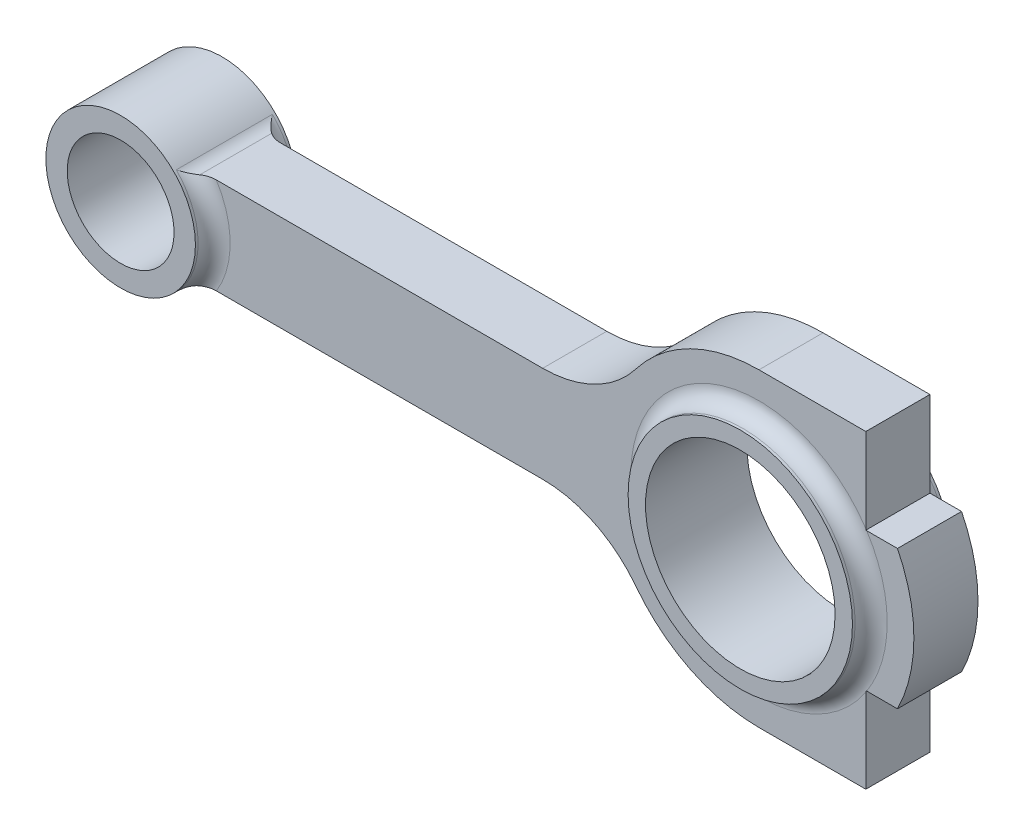
SolidWorks part; units mm, degrees
ref_plane "Front Plane" through (0, 0, 0) normal (0, 0, 1) x (1, 0, 0)
ref_plane "Top Plane" through (0, 0, 0) normal (0, 1, 0) x (1, 0, 0)
ref_plane "Right Plane" through (0, 0, 0) normal (1, 0, 0) x (0, 0, -1)
sketch "Sketch1" plane through (0, 0, 0) normal (0, 0, 1) x (1, 0, 0)
  line L0 (0, 0) -> (116, 0) construction
  line L1 (116, 29) -> (136, 29)
  line L2 (116, -29) -> (136, -29)
  line L4 (12.0416, 9) -> (75.5031, 9)
  line L5 (12.0416, -9) -> (75.5031, -9)
  line L7 (136, 29) -> (136, 13)
  line L8 (136, -29) -> (136, -13)
  line L9 (136, 13) -> (141.923, 13)
  line L10 (136, -13) -> (141.923, -13)
  circle A0 centre (0, 0) radius 10
  arc A1 (9.9166, 9.8824) -> (9.9166, -9.8824) centre (0, 0) ccw
  arc A2 (116, 29) -> (92.9723, 17.6275) centre (116, 0) ccw
  circle A3 centre (116, 0) radius 21
  circle A4 centre (116, 0) radius 17.75
  arc A5 (141.923, -13) -> (141.923, 13) centre (116, 0) ccw
  arc A6 (92.9723, -17.6275) -> (116, -29) centre (116, 0) ccw
  arc A7 (92.9723, 17.6275) -> (75.5031, 9) centre (75.5031, 31) cw
  arc A8 (92.9723, -17.6275) -> (75.5031, -9) centre (75.5031, -31) ccw
  arc A9 (9.9166, 9.8824) -> (12.0416, 9) centre (12.0416, 12) ccw
  arc A10 (9.9166, -9.8824) -> (12.0416, -9) centre (12.0416, -12) cw
  circle A11 centre (0, 0) radius 14
  dimension "D1" = 28
  dimension "D2" = 20
  dimension "D4" = 35.5
  dimension "D9" = 22
  dimension "D10" = 22
  dimension "D11" = 3
  dimension "D12" = 3
  dimension "D3" = 116
  dimension "D5" = 20
  dimension "D6" = 20
  dimension "D7" = 16
  dimension "D8" = 16
extrude "Boss-Extrude3" add sketch "Sketch1" along normal blind 12 contours A11 A10 L5 A8 A6 L2 L8 L10 A5 L9 L7 L1 A2 A7 L4 A9 A3 region at (82.8182, 0, 0)
extrude "Boss-Extrude6" add sketch "Sketch1<12>" along normal blind 15.5 contours A3
sketch "Sketch1<12>" plane through (0, 0, 0) normal (0, 0, 1) x (1, 0, 0) same geometry as "Sketch1"
extrude "Boss-Extrude7" add sketch "Sketch1<13>" against normal blind 3.5 contours A3
sketch "Sketch1<13>" plane through (0, 0, 0) normal (0, 0, 1) x (1, 0, 0) same geometry as "Sketch1"
extrude "Cut-Extrude2" cut sketch "Sketch1<15>" along normal mid plane 100 contours A4
sketch "Sketch1<15>" plane through (0, 0, 0) normal (0, 0, 1) x (1, 0, 0) same geometry as "Sketch1"
extrude "Boss-Extrude9" add sketch "Sketch1<17>" along normal blind 15.5 contours A11
sketch "Sketch1<17>" plane through (0, 0, 0) normal (0, 0, 1) x (1, 0, 0) same geometry as "Sketch1"
extrude "Boss-Extrude10" add sketch "Sketch1<18>" against normal blind 3.5 contours A11
sketch "Sketch1<18>" plane through (0, 0, 0) normal (0, 0, 1) x (1, 0, 0) same geometry as "Sketch1"
extrude "Cut-Extrude3" cut sketch "Sketch1<19>" against normal mid plane 100 contours A0
sketch "Sketch1<19>" plane through (0, 0, 0) normal (0, 0, 1) x (1, 0, 0) same geometry as "Sketch1"
fillet "Fillet1" radius 3 1 edges at (14, 0, 12)
fillet "Fillet2" radius 3 1 edges at (14, 0, 0)
fillet "Fillet3" radius 3 1 edges at (137, 0, 12)
fillet "Fillet4" radius 3 1 edges at (137, 0, 0)
